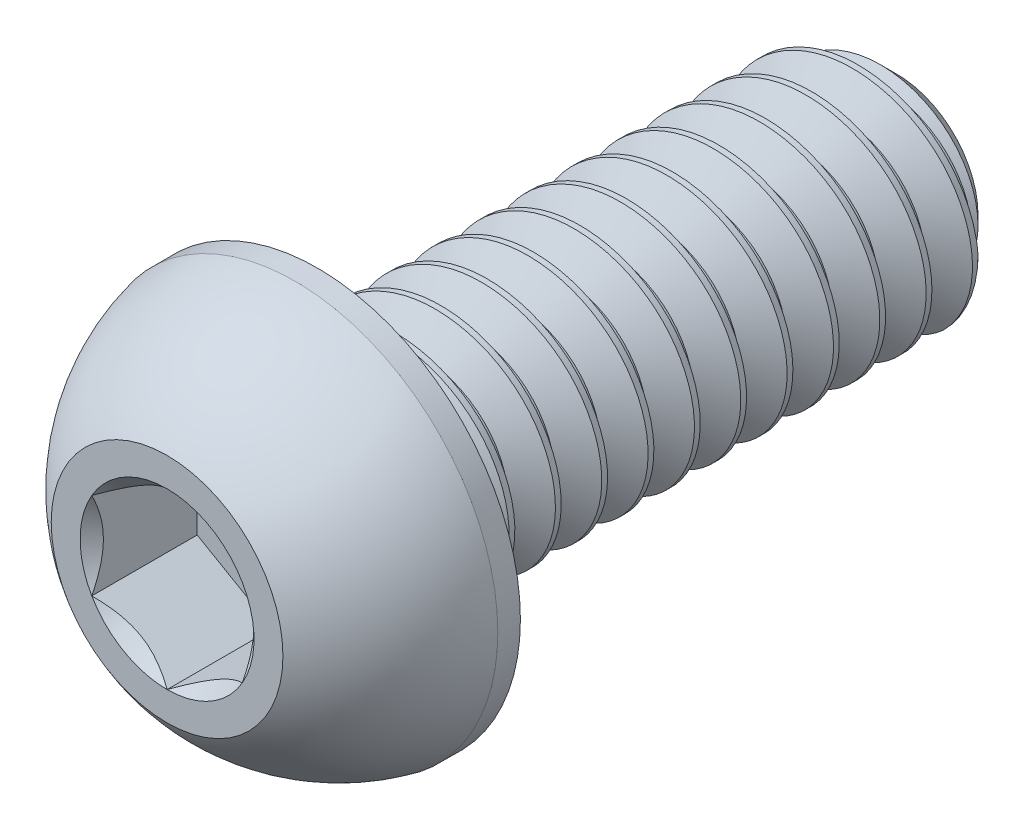
SolidWorks part; units mm, degrees
ref_plane "Front" through (0, 0, 0) normal (0, 0, 1) x (1, 0, 0)
ref_plane "Top" through (0, 0, 0) normal (0, 1, 0) x (1, 0, 0)
ref_plane "Right" through (0, 0, 0) normal (1, 0, 0) x (0, 0, -1)
sketch "Sketch1" plane through (0, 0, 0) normal (1, 0, 0) x (0, 0, -1)
  line L2 (1.3, 1) -> (6.3, 1)
  line L3 (6.3, 1) -> (6.3, 0)
  line L4 (6.3, 0) -> (1.3, 0)
  line L6 (1.105, 1.75) -> (1.3, 1.75) construction
  line L7 (6.3, 1) -> (6.3, -1) construction
  line L8 (0, 0) -> (1.3, 0) construction
  line L9 (1.3, 1.75) -> (1.3, -1.75) construction
  line L11 (1.3, 1) -> (1.3, 0)
  line L13 (0, 0.65) -> (0, -0.65) construction
  line L14 (0, 0.65) -> (0, 1) construction
  line L15 (6.275, 1.0433) -> (6.475, 0.6969) construction
  line L16 (6.475, 0.6969) -> (6.675, 1.0433) construction
  line L17 (6.675, 1.0433) -> (6.275, 1.0433) construction
  line L18 (6.3, 1) -> (6.65, 1) construction
  line L19 (6.475, 1.0433) -> (6.475, 1) construction
  line L20 (6.475, 1) -> (6.475, 0.7402) construction
  line L21 (6.475, 0.7402) -> (6.475, 0.6969) construction
  line L22 (6.45, 0.7402) -> (6.5, 0.7402)
  line L23 (6.2875, 1.0217) -> (6.6625, 1.0217)
  line L24 (6.5, 0.7402) -> (6.6625, 1.0217)
  line L25 (6.45, 0.7402) -> (6.2875, 1.0217)
  line L26 (6, 1) -> (6.3, 0.7)
  arc A3 (0, 1) -> (1.105, 1.75) centre (1.4858, 0) cw construction
  point P29 (6.475, 1.0217)
  point P30 (5.3, -1)
  dimension "D1" = 0.195
  dimension "Pitch" = 0.4
  dimension "D3" = 0.05
  dimension "D2" = 0.3
  dimension "D4" = 45
  dimension "D5" = 1
sketch "Sketch10" plane through (0, 0, 0) normal (1, 0, 0) x (0, 0, -1)
  line L0 (6, 1) -> (6.3, 0.7) construction
  line L1 (6, 1) -> (6.3, 0.7)
  line L4 (6.3, 1) -> (1.3, 1)
  line L5 (6.3, 0) -> (6.3, 1)
  line L6 (1.3, 0) -> (6.3, 0)
  line L7 (1.3, 1) -> (1.3, 0)
  line L8 (6, 1) -> (1.3, 1)
  line L9 (6.3, 0) -> (6.3, 0.7)
  line L10 (1.3, 0) -> (6.3, 0)
  line L11 (1.3, 1) -> (1.3, 0)
  dimension "D1" = 0
revolve "Revolve3" add sketch "Sketch10" angle 360 about L8
sketch "Sketch7" plane through (0, 0, 0) normal (1, 0, 0) x (0, 0, -1)
  line L6 (1.105, 1.75) -> (1.3, 1.75) construction
  line L8 (0, 0) -> (1.3, 0) construction
  line L11 (1.3, 1.75) -> (1.3, -1.75) construction
  line L12 (1.105, 1.75) -> (1.3, 1.75)
  line L13 (0, 0) -> (1.3, 0)
  line L14 (0, 0.65) -> (0, -0.65) construction
  line L15 (1.3, 1.75) -> (1.3, 0)
  line L16 (0, 1) -> (0, 0)
  arc A2 (1.105, 1.75) -> (0, 1) centre (1.4858, 0) ccw construction
  arc A3 (1.105, 1.75) -> (0, 1) centre (1.4858, 0) ccw
revolve "Revolve2" add sketch "Sketch7" angle 360 mid plane about L13
sketch "Sketch5" plane through (0, 0, 0) normal (0, 0, 1) x (1, 0, 0)
  line L1 (0.65, -0.3753) -> (0.65, 0.3753)
  line L2 (0.65, 0.3753) -> (0, 0.7506)
  line L3 (0, 0.7506) -> (-0.65, 0.3753)
  line L4 (-0.65, 0.3753) -> (-0.65, -0.3753)
  line L5 (-0.65, -0.3753) -> (0, -0.7506)
  line L6 (0, -0.7506) -> (0.65, -0.3753)
  circle A0 centre (0, 0) radius 0.65 construction
extrude "Cut-Extrude2" cut sketch "Sketch5" against normal blind 0.91
sketch "Sketch6" plane through (0, 0, 0) normal (0, 0, 1) x (1, 0, 0)
  circle A0 centre (0, 0) radius 0.7506
extrude "Cut-Extrude3" cut sketch "Sketch6" against normal blind 0.91 draft 45
sketch "Sketch9" plane through (0, 0, -1.3) normal (0, 0, -1) x (-1, 0, 0)
  circle A0 centre (0, 0) radius 1 construction
  circle A4 centre (0, 0) radius 1
split "Split1" bodies to split 113 resulting bodies 123 124 split by face at (1.75, 0, -1.3)
sketch "Sketch11" plane through (0, 0, -6.3) normal (0, 0, -1) x (-1, 0, 0)
  circle A0 centre (0, 0) radius 1 construction
  circle A1 centre (0, 0) radius 1
curve "Helix/Spiral1" pitch 0.4 height 6.3 radius 1 centre (0, 0, -6.3) axis (0, 0, 1) start towards (0, 1, 0)
sketch "Sketch12" plane through (0, 0, 0) normal (1, 0, 0) x (0, 0, -1)
  line L0 (6.45, 0.7402) -> (6.5, 0.7402) construction
  line L1 (6.5, 0.7402) -> (6.6625, 1.0217) construction
  line L2 (6.2875, 1.0217) -> (6.6625, 1.0217) construction
  line L3 (6.45, 0.7402) -> (6.2875, 1.0217) construction
  line L4 (6.45, 0.7402) -> (6.5, 0.7402)
  line L5 (6.5, 0.7402) -> (6.6625, 1.0217)
  line L6 (6.2875, 1.0217) -> (6.6625, 1.0217)
  line L7 (6.45, 0.7402) -> (6.2875, 1.0217)
sweep "Cut-Sweep2" cut profiles "Sketch12" path "Helix/Spiral1" align with end faces yes
extrude "Boss-Extrude1" add sketch "Sketch9" along normal blind 10 draft 45
equation "\"D1@Cut-Extrude2\" = \"Head Ht@Sketch1\" * .7"
equation "\"D1@Sketch1\" = \"Head Ht@Sketch1\" * .15"
equation "\"D1@Cut-Extrude3\" = \"D1@Cut-Extrude2\""
equation "\"D3@Sketch1\" = \"Pitch@Sketch1\" / 8"
equation "\"D2@Sketch1\"=\"Pitch@Sketch1\"*0.75"
equation "\"D3@Helix/Spiral1\" = \"Lg@Sketch1\" + \"Head Ht@Sketch1\""
equation "\"D4@Helix/Spiral1\"=\"pitch@sketch1\""
equation "\"D5@Sketch1\"=\"Pitch@Sketch1\"*2.5"
